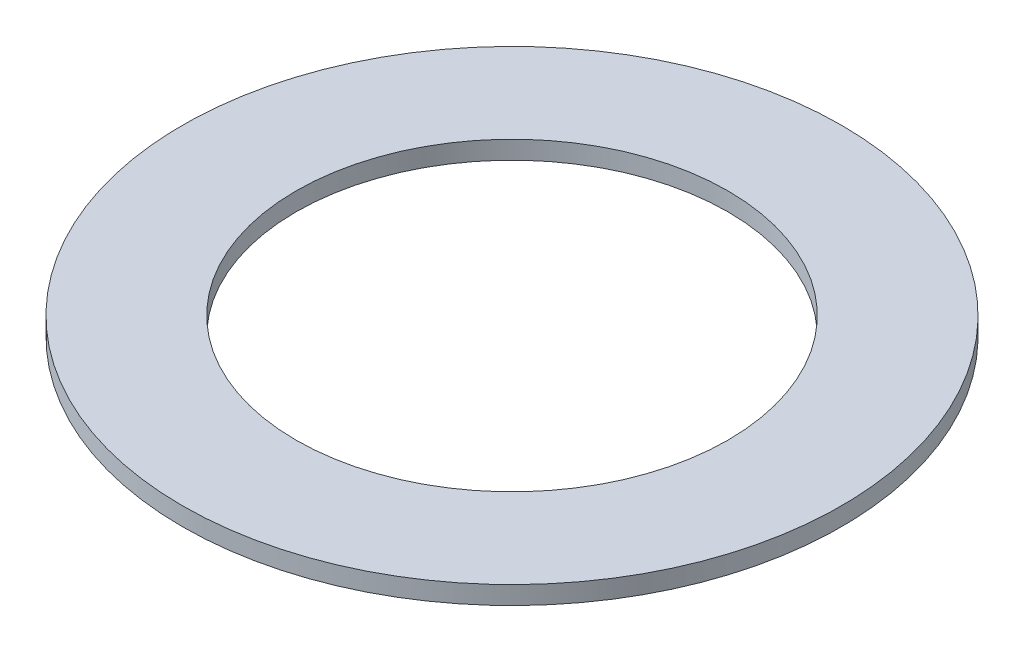
SolidWorks part; units mm, degrees
ref_plane "Front Plane" through (0, 0, 0) normal (0, 0, 1) x (1, 0, 0)
ref_plane "Top Plane" through (0, 0, 0) normal (0, 1, 0) x (1, 0, 0)
ref_plane "Right Plane" through (0, 0, 0) normal (1, 0, 0) x (0, 0, -1)
sketch "Sketch1" plane through (0, 0, 0) normal (0, 1, 0) x (1, 0, 0)
  circle A0 centre (0, 0) radius 72.5
  dimension "FLANGE_OD" = 145
extrude "Boss-Extrude1" add sketch "Sketch1" along normal blind 4
sketch "Sketch2" plane through (0, 0, 0) normal (0, 1, 0) x (1, 0, 0)
  circle A0 centre (0, 0) radius 47.5
  dimension "BORE_D" = 95
extrude "Cut-Extrude1" cut sketch "Sketch2" along normal through all
sketch "Sketch3" plane through (0, 4, 0) normal (0, 1, 0) x (1, 0, 0)
  circle A0 centre (0, 0) radius 28.4611 construction
  circle A1 centre (-28.4611, 0) radius 2.166
  dimension "BOLT_D" = 4.3321
  dimension "BOLT_PCD" = 56.9222
extrude "Cut-Extrude2" cut sketch "Sketch3" against normal blind 3.9701 rebuild error yes
pattern_circular "CirPattern1" count 6 over 360 rebuild error yes
